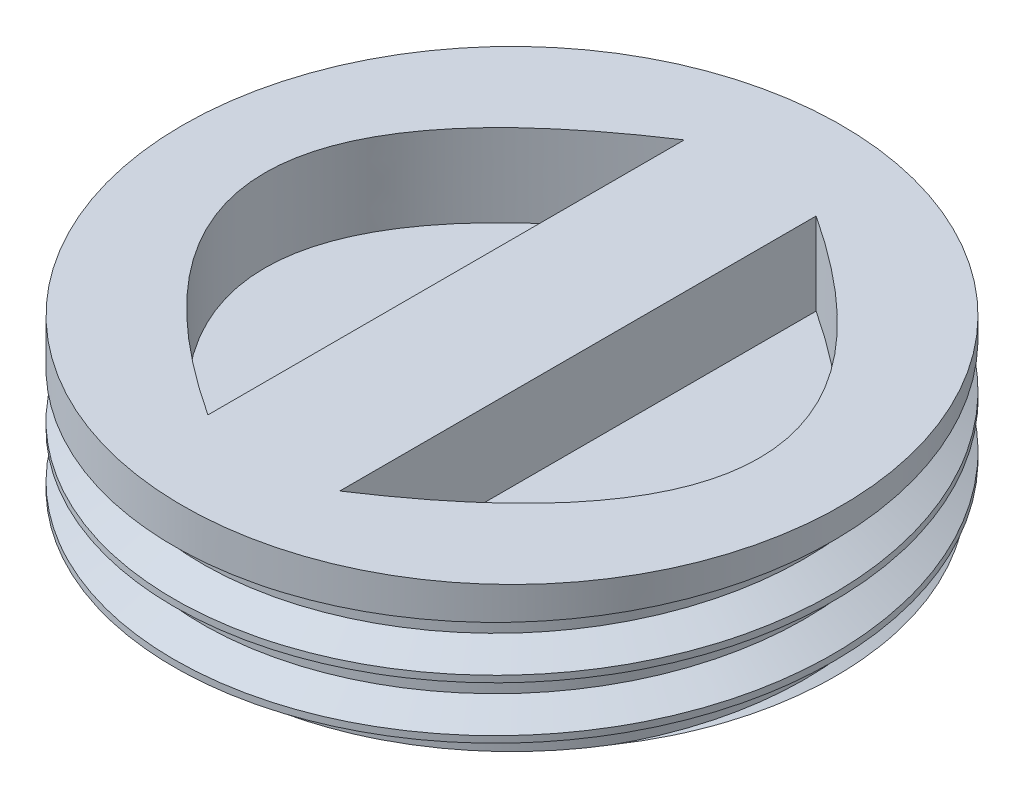
SolidWorks part; units mm, degrees
ref_plane "Front Plane" through (0, 0, 0) normal (0, 0, 1) x (1, 0, 0)
ref_plane "Top Plane" through (0, 0, 0) normal (0, 1, 0) x (1, 0, 0)
ref_plane "Right Plane" through (0, 0, 0) normal (1, 0, 0) x (0, 0, -1)
sketch "Sketch1" plane through (0, 0, 0) normal (0, 1, 0) x (1, 0, 0)
  circle A0 centre (-62.4172, 31.4468) radius 20
extrude "Boss-Extrude1" add sketch "Sketch1" along normal blind 10
thread "Thread1" pitch 3.175 method cut profile "Thread Profile1" start angle 0, offset 0, length 10, pitch 3.175, diameter 40
ref_plane "Plane1" through (-82.4172, 10, -31.4468) normal (0, 0, 1) x (-1, 0, 0)
sketch "Thread Profile1" plane through (-82.4172, 10, -31.4468) normal (0, 0, 1) x (-1, 0, 0)
  line L0 (0, 0) -> (0, 3.175) construction
  line L11 (0, 0) -> (0, 2.7781)
  line L12 (0, 2.7781) -> (-1.7185, 1.7859)
  line L13 (-1.7185, 1.7859) -> (-1.7185, 0.9922)
  line L15 (-1.7185, 0.9922) -> (0, 0)
  line L17 (-1.7185, 1.3891) -> (0, 1.3891) construction
  point P2 (0, 0)
  dimension "Pitch" = 3.175
  dimension "Profile_Angle" = 60
  dimension "Profile_Land" = 0.7937
  dimension "Profile_Height" = 1.7185
sketch "Sketch7" plane through (0, 10, 0) normal (0, 1, 0) x (1, 0, 0)
  line L0 (-66.4172, 45.9037) -> (-66.4172, 16.99)
  line L5 (-58.4172, 45.9037) -> (-58.4172, 16.99)
  line L6 (-62.4172, 46.4468) -> (-62.4172, 16.4468)
  line L7 (-47.4172, 31.4468) -> (-77.4172, 31.4468)
  circle A1 centre (-62.4172, 31.4468) radius 15
  circle A2 centre (-62.4172, 31.4468) radius 20 construction
  spline S0 degree 2 poles (-66.4172, 45.9037) (-62.4172, 46.99) (-58.4172, 45.9037) knots 0 0 0 1 1 1
  spline S1 degree 3 poles (-58.4172, 16.99) (-59.7506, 16.7184) (-62.4172, 16.1753) (-65.0839, 16.7184) (-66.4172, 16.99) knots 0 0 0 0 0.5 1 1 1 1
  point P4 (-62.4172, 31.8086)
  point P5 (-62.4172, 31.7305)
  point P6 (-62.4172, 31.7305)
  point P7 (-62.4172, 31.7305)
  dimension "D1" = 0
  dimension "D2" = 5
  dimension "D3" = 8
  dimension "D4" = 4
sketch "Sketch9" plane through (0, 10, 0) normal (0, 1, 0) x (1, 0, 0)
  line L0 (-66.4172, 45.9037) -> (-66.4172, 31.4468)
  line L1 (-66.4172, 45.9037) -> (-66.4172, 16.99) construction
  line L2 (-66.4172, 31.4468) -> (-66.4172, 16.99)
  line L3 (-58.4172, 45.9037) -> (-58.4172, 16.99)
  spline S0 degree 2 poles (-58.4172, 45.9037) (-36.4172, 31.4468) (-58.4172, 16.99) knots 0 0 0 1 1 1
  spline S1 degree 2 poles (-66.4172, 45.9037) (-88.4172, 31.4468) (-66.4172, 16.99) knots 0 0 0 1 1 1
extrude "Cut-Extrude2" cut sketch "Sketch9" against normal blind 5
